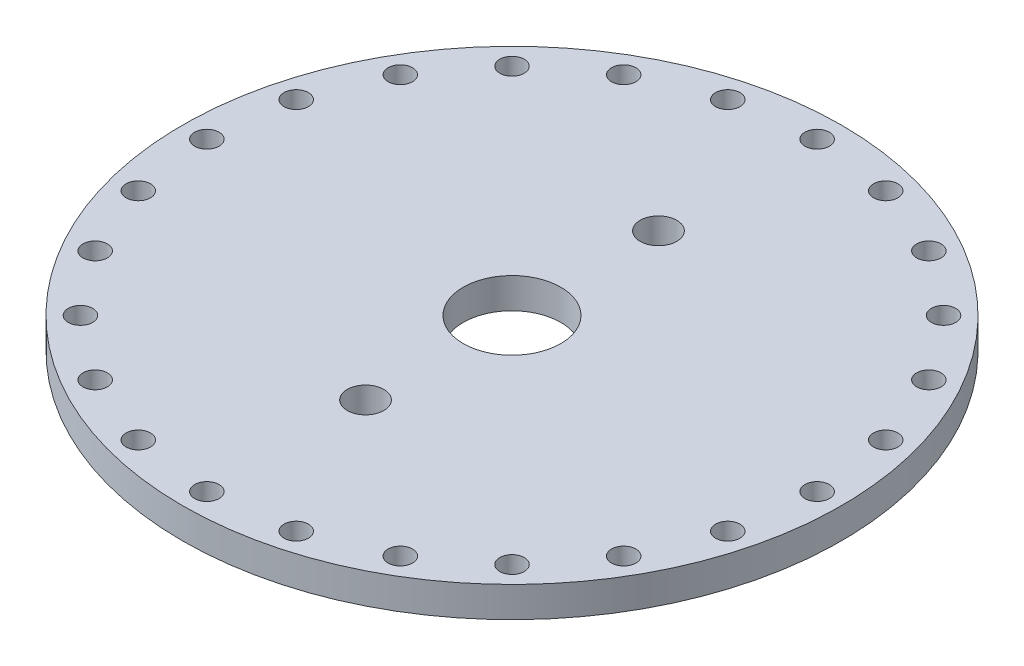
SolidWorks part; units mm, degrees
material "Plain Carbon Steel"
ref_plane "Front Plane" through (0, 0, 0) normal (0, 0, 1) x (1, 0, 0)
ref_plane "Top Plane" through (0, 0, 0) normal (0, 1, 0) x (1, 0, 0)
ref_plane "Right Plane" through (0, 0, 0) normal (1, 0, 0) x (0, 0, -1)
sketch "Sketch5" plane through (0, 0, 0) normal (0, 1, 0) x (1, 0, 0)
  line L0 (81.7617, 48.2039) -> (83.3467, 47.6336)
  line L1 (83.3467, 47.6336) -> (84.9242, 46.8612)
  line L2 (84.9242, 46.8612) -> (84.9242, 45.9559)
  line L3 (84.9242, 45.9559) -> (83.3467, 45.1835)
  line L4 (83.3467, 45.1835) -> (81.7617, 44.6133)
  line L5 (81.7617, 44.6133) -> (81.6895, 43.5108)
  line L6 (81.6895, 43.5108) -> (83.1864, 42.7385)
  line L7 (83.1864, 42.7385) -> (84.6497, 41.7667)
  line L8 (84.6497, 41.7667) -> (84.5315, 40.8693)
  line L9 (84.5315, 40.8693) -> (82.8666, 40.3094)
  line L10 (82.8666, 40.3094) -> (81.2208, 39.9508)
  line L11 (81.2208, 39.9508) -> (81.0053, 38.8673)
  line L12 (81.0053, 38.8673) -> (82.3886, 37.9063)
  line L13 (82.3886, 37.9063) -> (83.7125, 36.7518)
  line L14 (83.7125, 36.7518) -> (83.4782, 35.8774)
  line L15 (83.4782, 35.8774) -> (81.7544, 35.5396)
  line L16 (81.7544, 35.5396) -> (80.0759, 35.399)
  line L17 (80.0759, 35.399) -> (79.7208, 34.3529)
  line L18 (79.7208, 34.3529) -> (80.9669, 33.2194)
  line L19 (80.9669, 33.2194) -> (82.1288, 31.9021)
  line L20 (82.1288, 31.9021) -> (81.7824, 31.0658)
  line L21 (81.7824, 31.0658) -> (80.0292, 30.9558)
  line L22 (80.0292, 30.9558) -> (78.3466, 31.0354)
  line L23 (78.3466, 31.0354) -> (77.8581, 30.0446)
  line L24 (77.8581, 30.0446) -> (78.9455, 28.7583)
  line L25 (78.9455, 28.7583) -> (79.9255, 27.3005)
  line L26 (79.9255, 27.3005) -> (79.4729, 26.5166)
  line L27 (79.4729, 26.5166) -> (77.7205, 26.6363)
  line L28 (77.7205, 26.6363) -> (76.0626, 26.9349)
  line L29 (76.0626, 26.9349) -> (75.4489, 26.0164)
  line L30 (75.4489, 26.0164) -> (76.3593, 24.5991)
  line L31 (76.3593, 24.5991) -> (77.1405, 23.0259)
  line L32 (77.1405, 23.0259) -> (76.5895, 22.3078)
  line L33 (76.5895, 22.3078) -> (74.8677, 22.6553)
  line L34 (74.8677, 22.6553) -> (73.2631, 23.1677)
  line L35 (73.2631, 23.1677) -> (72.5346, 22.3371)
  line L36 (72.5346, 22.3371) -> (73.2522, 20.8132)
  line L37 (73.2522, 20.8132) -> (73.8214, 19.1514)
  line L38 (73.8214, 19.1514) -> (73.1813, 18.5113)
  line L39 (73.1813, 18.5113) -> (71.5196, 19.0806)
  line L40 (71.5196, 19.0806) -> (69.9957, 19.7981)
  line L41 (69.9957, 19.7981) -> (69.165, 19.0697)
  line L42 (69.165, 19.0697) -> (69.6775, 17.465)
  line L43 (69.6775, 17.465) -> (70.025, 15.7432)
  line L44 (70.025, 15.7432) -> (69.3068, 15.1922)
  line L45 (69.3068, 15.1922) -> (67.7336, 15.9735)
  line L46 (67.7336, 15.9735) -> (66.3163, 16.8839)
  line L47 (66.3163, 16.8839) -> (65.3978, 16.2701)
  line L48 (65.3978, 16.2701) -> (65.6964, 14.6123)
  line L49 (65.6964, 14.6123) -> (65.8161, 12.8598)
  line L50 (65.8161, 12.8598) -> (65.0322, 12.4072)
  line L51 (65.0322, 12.4072) -> (63.5745, 13.3872)
  line L52 (63.5745, 13.3872) -> (62.2881, 14.4747)
  line L53 (62.2881, 14.4747) -> (61.2973, 13.9861)
  line L54 (61.2973, 13.9861) -> (61.377, 12.3035)
  line L55 (61.377, 12.3035) -> (61.267, 10.5504)
  line L56 (61.267, 10.5504) -> (60.4307, 10.204)
  line L57 (60.4307, 10.204) -> (59.1134, 11.3658)
  line L58 (59.1134, 11.3658) -> (57.9798, 12.612)
  line L59 (57.9798, 12.612) -> (56.9338, 12.2569)
  line L60 (56.9338, 12.2569) -> (56.7931, 10.5783)
  line L61 (56.7931, 10.5783) -> (56.4553, 8.8546)
  line L62 (56.4553, 8.8546) -> (55.5809, 8.6203)
  line L63 (55.5809, 8.6203) -> (54.4264, 9.9441)
  line L64 (54.4264, 9.9441) -> (53.4654, 11.3275)
  line L65 (53.4654, 11.3275) -> (52.3819, 11.1119)
  line L66 (52.3819, 11.1119) -> (52.0234, 9.4661)
  line L67 (52.0234, 9.4661) -> (51.4634, 7.8013)
  line L68 (51.4634, 7.8013) -> (50.566, 7.683)
  line L69 (50.566, 7.683) -> (49.5942, 9.1463)
  line L70 (49.5942, 9.1463) -> (48.8219, 10.6433)
  line L71 (48.8219, 10.6433) -> (47.7195, 10.5711)
  line L72 (47.7195, 10.5711) -> (47.1492, 8.986)
  line L73 (47.1492, 8.986) -> (46.3768, 7.4086)
  line L74 (46.3768, 7.4086) -> (45.4715, 7.4086)
  line L75 (45.4715, 7.4086) -> (44.6991, 8.986)
  line L76 (44.6991, 8.986) -> (44.1289, 10.5711)
  line L77 (44.1289, 10.5711) -> (43.0264, 10.6433)
  line L78 (43.0264, 10.6433) -> (42.2541, 9.1463)
  line L79 (42.2541, 9.1463) -> (41.2823, 7.683)
  line L80 (41.2823, 7.683) -> (40.3849, 7.8013)
  line L81 (40.3849, 7.8013) -> (39.825, 9.4661)
  line L82 (39.825, 9.4661) -> (39.4664, 11.1119)
  line L83 (39.4664, 11.1119) -> (38.3829, 11.3275)
  line L84 (38.3829, 11.3275) -> (37.4219, 9.9441)
  line L85 (37.4219, 9.9441) -> (36.2674, 8.6203)
  line L86 (36.2674, 8.6203) -> (35.393, 8.8546)
  line L87 (35.393, 8.8546) -> (35.0552, 10.5783)
  line L88 (35.0552, 10.5783) -> (34.9146, 12.2569)
  line L89 (34.9146, 12.2569) -> (33.8685, 12.612)
  line L90 (33.8685, 12.612) -> (32.735, 11.3658)
  line L91 (32.735, 11.3658) -> (31.4177, 10.204)
  line L92 (31.4177, 10.204) -> (30.5814, 10.5504)
  line L93 (30.5814, 10.5504) -> (30.4714, 12.3035)
  line L94 (30.4714, 12.3035) -> (30.551, 13.9861)
  line L95 (30.551, 13.9861) -> (29.5602, 14.4747)
  line L96 (29.5602, 14.4747) -> (28.2739, 13.3872)
  line L97 (28.2739, 13.3872) -> (26.8161, 12.4072)
  line L98 (26.8161, 12.4072) -> (26.0322, 12.8598)
  line L99 (26.0322, 12.8598) -> (26.1519, 14.6123)
  line L100 (26.1519, 14.6123) -> (26.4505, 16.2701)
  line L101 (26.4505, 16.2701) -> (25.532, 16.8839)
  line L102 (25.532, 16.8839) -> (24.1147, 15.9735)
  line L103 (24.1147, 15.9735) -> (22.5415, 15.1922)
  line L104 (22.5415, 15.1922) -> (21.8234, 15.7432)
  line L105 (21.8234, 15.7432) -> (22.1709, 17.465)
  line L106 (22.1709, 17.465) -> (22.6833, 19.0697)
  line L107 (22.6833, 19.0697) -> (21.8527, 19.7981)
  line L108 (21.8527, 19.7981) -> (20.3288, 19.0806)
  line L109 (20.3288, 19.0806) -> (18.667, 18.5113)
  line L110 (18.667, 18.5113) -> (18.0269, 19.1514)
  line L111 (18.0269, 19.1514) -> (18.5962, 20.8132)
  line L112 (18.5962, 20.8132) -> (19.3137, 22.3371)
  line L113 (19.3137, 22.3371) -> (18.5853, 23.1677)
  line L114 (18.5853, 23.1677) -> (16.9806, 22.6553)
  line L115 (16.9806, 22.6553) -> (15.2588, 22.3078)
  line L116 (15.2588, 22.3078) -> (14.7078, 23.0259)
  line L117 (14.7078, 23.0259) -> (15.4891, 24.5991)
  line L118 (15.4891, 24.5991) -> (16.3995, 26.0164)
  line L119 (16.3995, 26.0164) -> (15.7857, 26.9349)
  line L120 (15.7857, 26.9349) -> (14.1279, 26.6363)
  line L121 (14.1279, 26.6363) -> (12.3754, 26.5166)
  line L122 (12.3754, 26.5166) -> (11.9228, 27.3005)
  line L123 (11.9228, 27.3005) -> (12.9028, 28.7583)
  line L124 (12.9028, 28.7583) -> (13.9903, 30.0446)
  line L125 (13.9903, 30.0446) -> (13.5017, 31.0354)
  line L126 (13.5017, 31.0354) -> (11.8191, 30.9558)
  line L127 (11.8191, 30.9558) -> (10.066, 31.0658)
  line L128 (10.066, 31.0658) -> (9.7196, 31.9021)
  line L129 (9.7196, 31.9021) -> (10.8814, 33.2194)
  line L130 (10.8814, 33.2194) -> (12.1276, 34.3529)
  line L131 (12.1276, 34.3529) -> (11.7725, 35.399)
  line L132 (11.7725, 35.399) -> (10.0939, 35.5396)
  line L133 (10.0939, 35.5396) -> (8.3702, 35.8774)
  line L134 (8.3702, 35.8774) -> (8.1359, 36.7518)
  line L135 (8.1359, 36.7518) -> (9.4597, 37.9063)
  line L136 (9.4597, 37.9063) -> (10.8431, 38.8673)
  line L137 (10.8431, 38.8673) -> (10.6275, 39.9508)
  line L138 (10.6275, 39.9508) -> (8.9817, 40.3094)
  line L139 (8.9817, 40.3094) -> (7.3169, 40.8693)
  line L140 (7.3169, 40.8693) -> (7.1986, 41.7667)
  line L141 (7.1986, 41.7667) -> (8.6619, 42.7385)
  line L142 (8.6619, 42.7385) -> (10.1589, 43.5108)
  line L143 (10.1589, 43.5108) -> (10.0867, 44.6133)
  line L144 (10.0867, 44.6133) -> (8.5016, 45.1835)
  line L145 (8.5016, 45.1835) -> (6.9242, 45.9559)
  line L146 (6.9242, 45.9559) -> (6.9242, 46.8612)
  line L147 (6.9242, 46.8612) -> (8.5016, 47.6336)
  line L148 (8.5016, 47.6336) -> (10.0867, 48.2039)
  line L149 (10.0867, 48.2039) -> (10.1589, 49.3063)
  line L150 (10.1589, 49.3063) -> (8.6619, 50.0786)
  line L151 (8.6619, 50.0786) -> (7.1986, 51.0504)
  line L152 (7.1986, 51.0504) -> (7.3169, 51.9478)
  line L153 (7.3169, 51.9478) -> (8.9817, 52.5078)
  line L154 (8.9817, 52.5078) -> (10.6275, 52.8663)
  line L155 (10.6275, 52.8663) -> (10.8431, 53.9498)
  line L156 (10.8431, 53.9498) -> (9.4597, 54.9108)
  line L157 (9.4597, 54.9108) -> (8.1359, 56.0653)
  line L158 (8.1359, 56.0653) -> (8.3702, 56.9397)
  line L159 (8.3702, 56.9397) -> (10.0939, 57.2775)
  line L160 (10.0939, 57.2775) -> (11.7725, 57.4182)
  line L161 (11.7725, 57.4182) -> (12.1276, 58.4642)
  line L162 (12.1276, 58.4642) -> (10.8814, 59.5978)
  line L163 (10.8814, 59.5978) -> (9.7196, 60.9151)
  line L164 (9.7196, 60.9151) -> (10.066, 61.7514)
  line L165 (10.066, 61.7514) -> (11.8191, 61.8614)
  line L166 (11.8191, 61.8614) -> (13.5017, 61.7817)
  line L167 (13.5017, 61.7817) -> (13.9903, 62.7725)
  line L168 (13.9903, 62.7725) -> (12.9028, 64.0589)
  line L169 (12.9028, 64.0589) -> (11.9228, 65.5166)
  line L170 (11.9228, 65.5166) -> (12.3754, 66.3005)
  line L171 (12.3754, 66.3005) -> (14.1279, 66.1808)
  line L172 (14.1279, 66.1808) -> (15.7857, 65.8822)
  line L173 (15.7857, 65.8822) -> (16.3995, 66.8007)
  line L174 (16.3995, 66.8007) -> (15.4891, 68.218)
  line L175 (15.4891, 68.218) -> (14.7078, 69.7912)
  line L176 (14.7078, 69.7912) -> (15.2588, 70.5094)
  line L177 (15.2588, 70.5094) -> (16.9806, 70.1619)
  line L178 (16.9806, 70.1619) -> (18.5853, 69.6494)
  line L179 (18.5853, 69.6494) -> (19.3137, 70.4801)
  line L180 (19.3137, 70.4801) -> (18.5962, 72.004)
  line L181 (18.5962, 72.004) -> (18.0269, 73.6657)
  line L182 (18.0269, 73.6657) -> (18.667, 74.3058)
  line L183 (18.667, 74.3058) -> (20.3288, 73.7366)
  line L184 (20.3288, 73.7366) -> (21.8527, 73.019)
  line L185 (21.8527, 73.019) -> (22.6833, 73.7475)
  line L186 (22.6833, 73.7475) -> (22.1709, 75.3521)
  line L187 (22.1709, 75.3521) -> (21.8234, 77.0739)
  line L188 (21.8234, 77.0739) -> (22.5415, 77.6249)
  line L189 (22.5415, 77.6249) -> (24.1147, 76.8437)
  line L190 (24.1147, 76.8437) -> (25.532, 75.9333)
  line L191 (25.532, 75.9333) -> (26.4505, 76.547)
  line L192 (26.4505, 76.547) -> (26.1519, 78.2049)
  line L193 (26.1519, 78.2049) -> (26.0322, 79.9573)
  line L194 (26.0322, 79.9573) -> (26.8161, 80.4099)
  line L195 (26.8161, 80.4099) -> (28.2739, 79.4299)
  line L196 (28.2739, 79.4299) -> (29.5602, 78.3425)
  line L197 (29.5602, 78.3425) -> (30.551, 78.831)
  line L198 (30.551, 78.831) -> (30.4714, 80.5136)
  line L199 (30.4714, 80.5136) -> (30.5814, 82.2668)
  line L200 (30.5814, 82.2668) -> (31.4177, 82.6132)
  line L201 (31.4177, 82.6132) -> (32.735, 81.4513)
  line L202 (32.735, 81.4513) -> (33.8685, 80.2052)
  line L203 (33.8685, 80.2052) -> (34.9146, 80.5603)
  line L204 (34.9146, 80.5603) -> (35.0552, 82.2388)
  line L205 (35.0552, 82.2388) -> (35.393, 83.9626)
  line L206 (35.393, 83.9626) -> (36.2674, 84.1969)
  line L207 (36.2674, 84.1969) -> (37.4219, 82.8731)
  line L208 (37.4219, 82.8731) -> (38.3829, 81.4897)
  line L209 (38.3829, 81.4897) -> (39.4664, 81.7052)
  line L210 (39.4664, 81.7052) -> (39.825, 83.351)
  line L211 (39.825, 83.351) -> (40.3849, 85.0159)
  line L212 (40.3849, 85.0159) -> (41.2823, 85.1341)
  line L213 (41.2823, 85.1341) -> (42.2541, 83.6708)
  line L214 (42.2541, 83.6708) -> (43.0264, 82.1739)
  line L215 (43.0264, 82.1739) -> (44.1289, 82.2461)
  line L216 (44.1289, 82.2461) -> (44.6991, 83.8311)
  line L217 (44.6991, 83.8311) -> (45.4715, 85.4086)
  line L218 (45.4715, 85.4086) -> (46.3768, 85.4086)
  line L219 (46.3768, 85.4086) -> (47.1492, 83.8311)
  line L220 (47.1492, 83.8311) -> (47.7195, 82.2461)
  line L221 (47.7195, 82.2461) -> (48.8219, 82.1739)
  line L222 (48.8219, 82.1739) -> (49.5942, 83.6708)
  line L223 (49.5942, 83.6708) -> (50.566, 85.1341)
  line L224 (50.566, 85.1341) -> (51.4634, 85.0159)
  line L225 (51.4634, 85.0159) -> (52.0234, 83.351)
  line L226 (52.0234, 83.351) -> (52.3819, 81.7052)
  line L227 (52.3819, 81.7052) -> (53.4654, 81.4897)
  line L228 (53.4654, 81.4897) -> (54.4264, 82.8731)
  line L229 (54.4264, 82.8731) -> (55.5809, 84.1969)
  line L230 (55.5809, 84.1969) -> (56.4553, 83.9626)
  line L231 (56.4553, 83.9626) -> (56.7931, 82.2388)
  line L232 (56.7931, 82.2388) -> (56.9338, 80.5603)
  line L233 (56.9338, 80.5603) -> (57.9798, 80.2052)
  line L234 (57.9798, 80.2052) -> (59.1134, 81.4513)
  line L235 (59.1134, 81.4513) -> (60.4307, 82.6132)
  line L236 (60.4307, 82.6132) -> (61.267, 82.2668)
  line L237 (61.267, 82.2668) -> (61.377, 80.5136)
  line L238 (61.377, 80.5136) -> (61.2973, 78.831)
  line L239 (61.2973, 78.831) -> (62.2881, 78.3425)
  line L240 (62.2881, 78.3425) -> (63.5745, 79.4299)
  line L241 (63.5745, 79.4299) -> (65.0322, 80.4099)
  line L242 (65.0322, 80.4099) -> (65.8161, 79.9573)
  line L243 (65.8161, 79.9573) -> (65.6964, 78.2049)
  line L244 (65.6964, 78.2049) -> (65.3978, 76.547)
  line L245 (65.3978, 76.547) -> (66.3163, 75.9333)
  line L246 (66.3163, 75.9333) -> (67.7336, 76.8437)
  line L247 (67.7336, 76.8437) -> (69.3068, 77.6249)
  line L248 (69.3068, 77.6249) -> (70.025, 77.0739)
  line L249 (70.025, 77.0739) -> (69.6775, 75.3521)
  line L250 (69.6775, 75.3521) -> (69.165, 73.7475)
  line L251 (69.165, 73.7475) -> (69.9957, 73.019)
  line L252 (69.9957, 73.019) -> (71.5196, 73.7366)
  line L253 (71.5196, 73.7366) -> (73.1813, 74.3058)
  line L254 (73.1813, 74.3058) -> (73.8214, 73.6657)
  line L255 (73.8214, 73.6657) -> (73.2522, 72.004)
  line L256 (73.2522, 72.004) -> (72.5346, 70.4801)
  line L257 (72.5346, 70.4801) -> (73.2631, 69.6494)
  line L258 (73.2631, 69.6494) -> (74.8677, 70.1619)
  line L259 (74.8677, 70.1619) -> (76.5895, 70.5094)
  line L260 (76.5895, 70.5094) -> (77.1405, 69.7912)
  line L261 (77.1405, 69.7912) -> (76.3593, 68.218)
  line L262 (76.3593, 68.218) -> (75.4489, 66.8007)
  line L263 (75.4489, 66.8007) -> (76.0626, 65.8822)
  line L264 (76.0626, 65.8822) -> (77.7205, 66.1808)
  line L265 (77.7205, 66.1808) -> (79.4729, 66.3005)
  line L266 (79.4729, 66.3005) -> (79.9255, 65.5166)
  line L267 (79.9255, 65.5166) -> (78.9455, 64.0589)
  line L268 (78.9455, 64.0589) -> (77.8581, 62.7725)
  line L269 (77.8581, 62.7725) -> (78.3466, 61.7817)
  line L270 (78.3466, 61.7817) -> (80.0292, 61.8614)
  line L271 (80.0292, 61.8614) -> (81.7824, 61.7514)
  line L272 (81.7824, 61.7514) -> (82.1288, 60.9151)
  line L273 (82.1288, 60.9151) -> (80.9669, 59.5978)
  line L274 (80.9669, 59.5978) -> (79.7208, 58.4642)
  line L275 (79.7208, 58.4642) -> (80.0759, 57.4182)
  line L276 (80.0759, 57.4182) -> (81.7544, 57.2775)
  line L277 (81.7544, 57.2775) -> (83.4782, 56.9397)
  line L278 (83.4782, 56.9397) -> (83.7125, 56.0653)
  line L279 (83.7125, 56.0653) -> (82.3886, 54.9108)
  line L280 (82.3886, 54.9108) -> (81.0053, 53.9498)
  line L281 (81.0053, 53.9498) -> (81.2208, 52.8663)
  line L282 (81.2208, 52.8663) -> (82.8666, 52.5078)
  line L283 (82.8666, 52.5078) -> (84.5315, 51.9478)
  line L284 (84.5315, 51.9478) -> (84.6497, 51.0504)
  line L285 (84.6497, 51.0504) -> (83.1864, 50.0786)
  line L286 (83.1864, 50.0786) -> (81.6895, 49.3063)
  line L287 (81.6895, 49.3063) -> (81.7617, 48.2039)
  line L288 (45.9242, 85.4086) -> (45.9242, 7.4086) construction
  line L289 (6.9242, 46.4086) -> (84.9242, 46.4086) construction
  point P292 (45.9242, 46.4086)
sketch "Sketch6" plane through (0, 0, 0) normal (0, 1, 0) x (1, 0, 0)
  line L0 (45.9242, 85.4086) -> (45.9242, 7.4086) construction
  circle A0 centre (45.9242, 46.4086) radius 4
  dimension "D1" = 8
sketch "Sketch7" plane through (0, 0, 0) normal (0, 1, 0) x (1, 0, 0)
  line L0 (45.9242, 85.4086) -> (45.9242, 7.4086) construction
  line L1 (25.4921, 46.4086) -> (64.6594, 46.4086) construction
  line L2 (6.9242, 46.4086) -> (84.9242, 46.4086) construction
  circle A0 centre (45.9242, 58.4086) radius 1.5
  circle A1 centre (45.9242, 34.4086) radius 1.5
  dimension "D2" = 3
  dimension "D1" = 12
sketch "Sketch8" plane through (0, 0, 0) normal (0, 1, 0) x (1, 0, 0)
  line L0 (6.9242, 46.4086) -> (84.9242, 46.4086) construction
  circle A0 centre (45.9242, 46.4086) radius 27
  dimension "D1" = 54
sketch "Sketch9" plane through (0, 0, 0) normal (0, 1, 0) x (1, 0, 0)
  line L0 (45.9242, 85.4086) -> (45.9242, 7.4086) construction
  line L1 (45.9242, 71.4086) -> (45.9242, 73.4086) construction
  circle A0 centre (45.9242, 71.4086) radius 1
  circle A1 centre (45.9242, 46.4086) radius 27 construction
  circle A2 centre (52.3946, 70.5567) radius 1
  circle A3 centre (58.4242, 68.0592) radius 1
  circle A4 centre (63.6018, 64.0862) radius 1
  circle A5 centre (67.5748, 58.9086) radius 1
  circle A6 centre (70.0723, 52.8791) radius 1
  circle A7 centre (70.9242, 46.4086) radius 1
  circle A8 centre (70.0723, 39.9381) radius 1
  circle A9 centre (67.5748, 33.9086) radius 1
  circle A10 centre (63.6018, 28.7309) radius 1
  circle A11 centre (58.4242, 24.7579) radius 1
  circle A12 centre (52.3946, 22.2604) radius 1
  circle A13 centre (45.9242, 21.4086) radius 1
  circle A14 centre (39.4537, 22.2604) radius 1
  circle A15 centre (33.4242, 24.7579) radius 1
  circle A16 centre (28.2465, 28.7309) radius 1
  circle A17 centre (24.2735, 33.9086) radius 1
  circle A18 centre (21.776, 39.9381) radius 1
  circle A19 centre (20.9242, 46.4086) radius 1
  circle A20 centre (21.776, 52.8791) radius 1
  circle A21 centre (24.2735, 58.9086) radius 1
  circle A22 centre (28.2465, 64.0862) radius 1
  circle A23 centre (33.4242, 68.0592) radius 1
  circle A24 centre (39.4537, 70.5567) radius 1
  point P55 (45.9242, 46.4086)
  dimension "D1" = 2
  dimension "D2" = 2
  dimension "D3" = 24
extrude "Boss-Extrude1" add sketch "Sketch8" along normal blind 2.5
extrude "Boss-Extrude2" [suppressed] add sketch "Sketch5" along normal up to surface (2.5 mm away) up to face at (45.9242, 2.5, -19.4086)
extrude "Cut-Extrude1" cut sketch "Sketch6" along normal up to next
extrude "Cut-Extrude2" cut sketch "Sketch7" along normal blind 2.5
extrude "Cut-Extrude3" cut sketch "Sketch9" along normal blind 2.5
